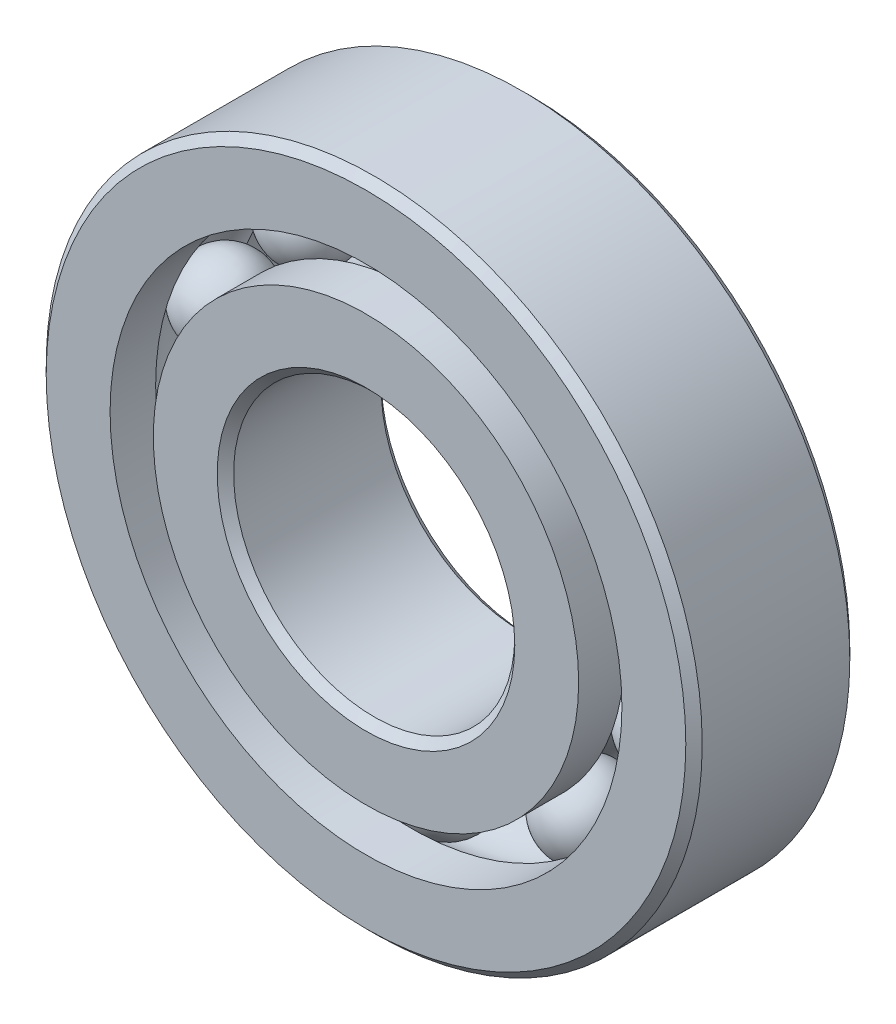
SolidWorks part; units mm, degrees
ref_plane "Front Plane" through (0, 0, 0) normal (0, 0, 1) x (1, 0, 0)
ref_plane "Top Plane" through (0, 0, 0) normal (0, 1, 0) x (1, 0, 0)
ref_plane "Right Plane" through (0, 0, 0) normal (1, 0, 0) x (0, 0, -1)
sketch "Sketch1" plane through (0, 0, 0) normal (1, 0, 0) x (0, 0, -1)
  line L0 (-2.7781, 0) -> (2.7781, 0) construction
  line L1 (0, 11.1125) -> (0, -11.1125) construction
  line L2 (2.5003, 11.1125) -> (-2.5003, 11.1125)
  line L3 (-2.5003, 11.1125) -> (-2.7781, 10.8347)
  line L4 (-2.7781, 10.8347) -> (-2.7781, 8.6702)
  line L5 (-2.7781, 8.6702) -> (-1.2347, 8.6702)
  line L6 (2.7781, 8.6702) -> (1.2347, 8.6702)
  line L7 (2.7781, 10.8347) -> (2.7781, 8.6702)
  line L8 (2.5003, 11.1125) -> (2.7781, 10.8347)
  line L9 (0, 11.1125) -> (0, 7.9375) construction
  line L10 (0, 7.9375) -> (0, 4.7625) construction
  arc A0 (-1.2347, 8.6702) -> (1.2347, 8.6702) centre (0, 7.9375) cw
  point P14 (0, 4.7625)
  dimension "Width" = 5.5562
  dimension "OD" = 22.225
  dimension "D1" = 45
  dimension "D2" = 0.2778
  dimension "Shaft Dia" = 9.525
  dimension "D3" = 2.4694
  dimension "D4" = 0.7327
revolve "Revolve1" add sketch "Sketch1" angle 360 about L0
sketch "Sketch3" plane through (0, 0, 0) normal (1, 0, 0) x (0, 0, -1)
  line L0 (-2.7781, 7.2048) -> (-1.2347, 7.2048)
  line L1 (0, 11.1125) -> (0, -11.1125) construction
  line L2 (-2.7781, 10.8347) -> (-2.7781, 8.6702) construction
  line L3 (-2.7781, 7.2048) -> (-2.7781, 5.0403)
  line L4 (-2.5003, 11.1125) -> (-2.7781, 10.8347) construction
  line L5 (-2.7781, 5.0403) -> (-2.5003, 4.7625)
  line L6 (-2.5003, 4.7625) -> (2.5003, 4.7625)
  line L7 (2.5003, 11.1125) -> (2.5003, -11.1125) construction
  line L8 (2.5003, 4.7625) -> (2.7781, 5.0403)
  line L9 (2.7781, -10.8347) -> (2.7781, 10.8347) construction
  line L10 (2.7781, 5.0403) -> (2.7781, 7.2048)
  line L11 (2.7781, 7.2048) -> (1.2347, 7.2048)
  line L13 (2.5003, 11.1125) -> (2.7781, 10.8347) construction
  arc A0 (1.2347, 8.6702) -> (-1.2347, 8.6702) centre (0, 7.9375) ccw construction
  arc A1 (1.2347, 7.2048) -> (-1.2347, 7.2048) centre (0, 7.9375) cw
revolve "Revolve3" add sketch "Sketch3" angle 360 about L0
sketch "Sketch4" plane through (0, 0, 0) normal (1, 0, 0) x (0, 0, -1)
  line L0 (-1.4357, 7.9375) -> (1.4357, 7.9375)
  arc A2 (-1.4357, 7.9375) -> (1.4357, 7.9375) centre (0, 7.9375) cw
  arc A3 (1.2347, 8.6702) -> (-1.2347, 8.6702) centre (0, 7.9375) ccw construction
revolve "Revolve4" add sketch "Sketch4" angle 360 about L0
ref_axis "Axis1" through (0, 0, -2.7781) along (0, 0, 1)
pattern_circular "CirPattern1" count 10 every 36 about axis through (0, 0, -2.7781) along (0, 0, 1) of bodies 104
sketch "Sketch5" plane through (0, 0, 0) normal (1, 0, 0) x (0, 0, -1)
  line L0 (-2.7781, 8.6702) -> (-1.2347, 8.6702) construction
  line L1 (-2.6392, 8.6702) -> (-1.4357, 8.6702)
  line L2 (-2.6392, 8.6702) -> (-2.6392, 7.2048)
  line L3 (-2.6392, 7.2048) -> (-1.4357, 7.2048)
  line L4 (-1.4357, 8.6702) -> (-1.4357, 7.2048)
  line L5 (-2.7781, 7.2048) -> (-1.2347, 7.2048) construction
  line L6 (2.7781, 8.6702) -> (1.2347, 8.6702) construction
  line L7 (2.6392, 8.6702) -> (1.4357, 8.6702)
  line L8 (2.6392, 8.6702) -> (2.6392, 7.2048)
  line L9 (2.6392, 7.2048) -> (1.4357, 7.2048)
  line L10 (1.4357, 8.6702) -> (1.4357, 7.2048)
  line L11 (2.7781, 7.2048) -> (1.2347, 7.2048) construction
  line L12 (-2.5003, 11.1125) -> (-2.7781, 10.8347) construction
  point P18 (-2.6392, 10.9736)
revolve "Revolve5" [suppressed] add sketch "Sketch5" angle 360 about L0
equation "\"D2@Sketch1\" = \"Width@Sketch1\"*.05"
equation "\"D3@Sketch1\" = \"Width@Sketch1\"/2.25"
equation "\"D4@Sketch1\" = (((\"OD@Sketch1\"-\"Width@Sketch1\")/2)/3.25)/3.5"
equation "\"D2@CirPattern1\" = 360/\"Balls@CirPattern1\""
